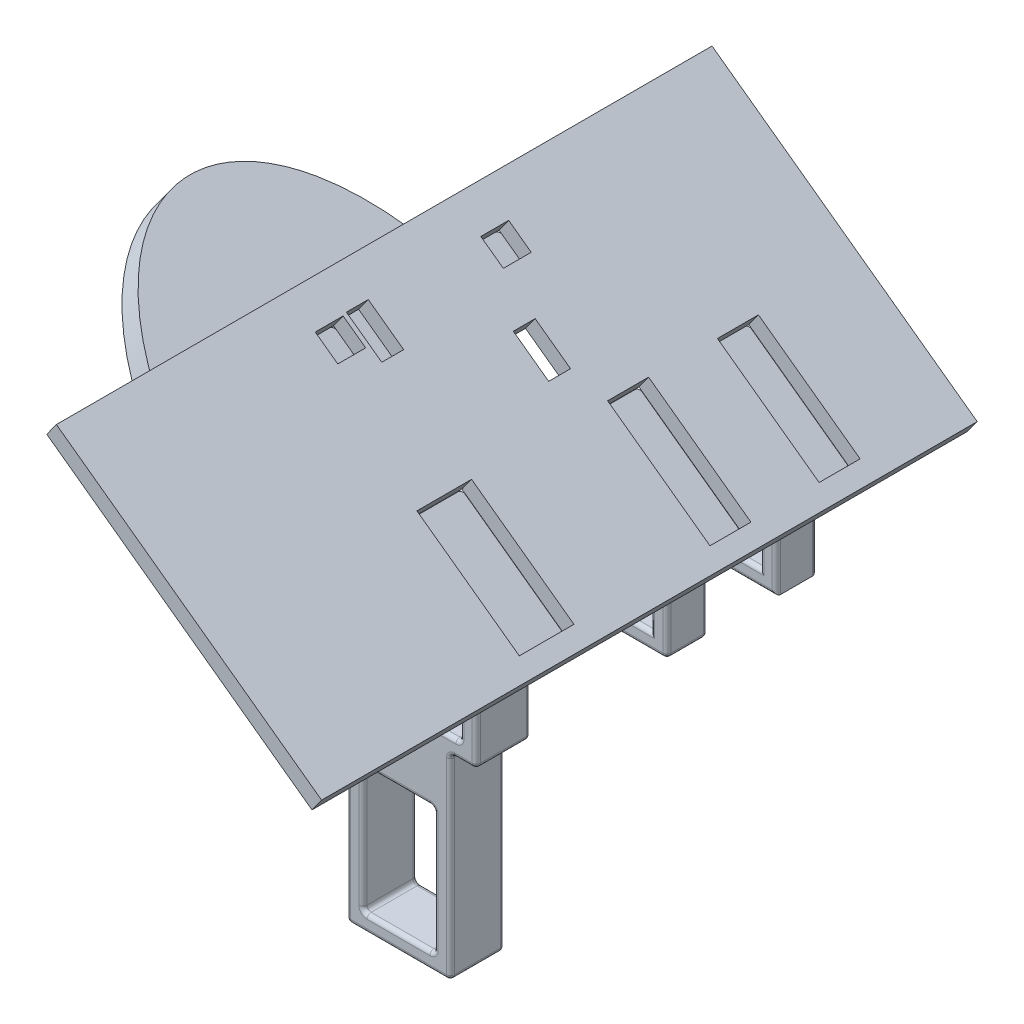
SolidWorks part; units mm, degrees
ref_plane "Front Plane" through (0, 0, 0) normal (0, 0, 1) x (1, 0, 0)
ref_plane "Top Plane" through (0, 0, 0) normal (0, 1, 0) x (1, 0, 0)
ref_plane "Right Plane" through (0, 0, 0) normal (1, 0, 0) x (0, 0, -1)
sketch "Sketch3" plane through (0, 0, 0) normal (0, 0, 1) x (1, 0, 0)
  line L0 (-14.25, 5.65) -> (14.25, 5.65) construction
  line L1 (-11.25, -2.65) -> (11.25, -2.65)
  line L2 (-11.25, -2.65) -> (-11.25, 2.65)
  line L3 (-11.25, 2.65) -> (11.25, 2.65)
  line L4 (11.25, -2.65) -> (11.25, 2.65)
  line L5 (-11.25, -2.65) -> (11.25, 2.65) construction
  line L6 (-11.25, 2.65) -> (11.25, -2.65) construction
  line L7 (-6.5, -15.45) -> (6.5, -15.45)
  line L8 (-6.5, -15.45) -> (-6.5, -38.55)
  line L9 (-6.5, -38.55) -> (6.5, -38.55)
  line L10 (6.5, -15.45) -> (6.5, -38.55)
  line L11 (-6.5, -15.45) -> (6.5, -38.55) construction
  line L12 (-6.5, -38.55) -> (6.5, -15.45) construction
  line L13 (14.25, -5.65) -> (14.25, 5.65)
  line L15 (-14.25, -5.65) -> (-14.25, 5.65)
  line L16 (9.5, -12.45) -> (9.5, -41.55)
  line L17 (-9.5, -41.55) -> (9.5, -41.55)
  line L18 (-9.5, -12.45) -> (-9.5, -41.55)
  line L20 (-9.5, -12.45) -> (9.5, -12.45) construction
  line L21 (-14.25, -5.65) -> (14.25, -5.65) construction
  line L22 (-9.5, -12.45) -> (-9.5, -5.65)
  line L23 (-9.5, -5.65) -> (-14.25, -5.65)
  line L24 (14.25, -5.65) -> (9.5, -5.65)
  line L25 (9.5, -5.65) -> (9.5, -12.45)
  line L26 (-14.25, 5.65) -> (1.7036, 27.6082)
  line L27 (1.7036, 27.6082) -> (20.3571, 14.0557)
  line L28 (20.3571, 14.0557) -> (14.25, 5.65)
  line L29 (0, -41.55) -> (0, 5.7) construction
  point P0 (0, 0)
  point P5 (0, -27)
  dimension "D1" = 22.5
  dimension "D2" = 5.3
  dimension "D3" = 27
  dimension "D4" = 13
  dimension "D5" = 23.1
  dimension "D7" = 3
  dimension "D8" = 54
  dimension "D9" = 10.39
  dimension "D10" = 8.4057
  dimension "D11" = 19
  dimension "D6" = 3
extrude "Boss-Extrude1" add sketch "Sketch3" along normal blind 9.9
sketch "Sketch4" plane through (13.7171, 18.8799, 0) normal (0.5878, 0.809, 0) x (0.809, -0.5878, 0)
  line L0 (-3.321, 0) -> (-3.321, -9.9) construction
  line L1 (8.2075, 0) -> (-14.8495, 0) construction
  line L2 (8.2075, -9.9) -> (-14.8495, -9.9) construction
  line L3 (-14.8495, -4.95) -> (8.2075, -4.95) construction
  line L4 (-14.8495, -9.9) -> (-14.8495, 0) construction
  line L5 (8.2075, -9.9) -> (8.2075, 0) construction
  line L7 (-48.321, 71.1) -> (11.679, 71.1)
  line L8 (-48.321, 71.1) -> (-48.321, -48.9)
  line L9 (-48.321, -48.9) -> (11.679, -48.9)
  line L10 (11.679, 71.1) -> (11.679, -48.9)
  line L11 (-48.321, 71.1) -> (11.679, -48.9) construction
  line L12 (-48.321, -48.9) -> (11.679, 71.1) construction
  point P12 (-3.321, -4.95)
  point P13 (-18.321, 11.1)
  dimension "D1" = 120
  dimension "D2" = 60
  dimension "D3" = 16.05
  dimension "D4" = 15
extrude "Boss-Extrude2" add sketch "Sketch4" along normal blind 3
sketch "Sketch7" plane through (13.7171, 18.8799, 0) normal (-0.5878, -0.809, 0) x (0.809, -0.5878, 0)
  line L0 (-14.9179, -11.1) -> (-63.9179, -11.1) construction
  line L1 (-48.321, 48.9) -> (11.679, 48.9) construction
  line L6 (-36.7569, 1.65) -> (-41.8569, 1.65)
  line L7 (-36.7569, 1.65) -> (-36.7569, 6.75)
  line L8 (-36.7569, 6.75) -> (-41.8569, 6.75)
  line L9 (-41.8569, 1.65) -> (-41.8569, 6.75)
  line L10 (-36.7569, 1.65) -> (-41.8569, 6.75) construction
  line L11 (-36.7569, 6.75) -> (-41.8569, 1.65) construction
  line L12 (-48.321, -71.1) -> (-48.321, 48.9) construction
  line L13 (-36.7569, -23.55) -> (-36.7569, -28.65)
  line L14 (-36.7569, -23.55) -> (-41.8569, -23.55)
  line L15 (-41.8569, -23.55) -> (-41.8569, -28.65)
  line L16 (-36.7569, -28.65) -> (-41.8569, -28.65)
  line L17 (-41.8569, -23.55) -> (-36.7569, -28.65) construction
  point P4 (-39.3069, 3.9)
  point P10 (-39.3069, -26.1)
  point P11 (-39.3069, 4.2)
  dimension "D1" = 15
  dimension "D2" = 9.0141
  dimension "D3" = 5.1
  dimension "D4" = 5.1
  dimension "D5" = 5.1
  dimension "D6" = 6.4641
  dimension "D7" = 12.45
  dimension "D8" = 60
  dimension "D9" = 30.3
extrude "Boss-Extrude3" add sketch "Sketch7" along normal blind 24.5 and the other way blind 3
sketch "Sketch8" plane through (-0.6837, -0.941, 0) normal (-0.5878, -0.809, 0) x (0.809, -0.5878, 0)
  line L2 (-23.3069, 5.8504) -> (-23.3069, -28.0504)
  line L3 (-23.3069, 5.8504) -> (-34.6206, 17.1641)
  line L4 (-23.3069, -28.0504) -> (-34.6206, -39.3641)
  line L6 (11.679, -71.1) -> (-48.321, -71.1) construction
  line L7 (-48.321, 48.9) -> (11.679, -71.1) construction
  line L8 (-18.321, -11.1) -> (-48.321, -11.1) construction
  line L9 (11.679, 48.9) -> (11.679, -71.1) construction
  ellipse E0 centre (-23.3069, -11.1) end of major axis (-72.2778, -11.1) minor radius 29.05 (-34.6206, 17.1641) -> (-34.6206, -39.3641) ccw
  dimension "D1" = 4.9859
  dimension "D2" = 28.2641
  dimension "D3" = 23.9569
  dimension "D4" = 45
  dimension "D5" = 16
  dimension "D6" = 48.9709
  dimension "D7" = 60
  dimension "D8" = 34.9859
extrude "Boss-Extrude4" add sketch "Sketch8" along normal blind 5
ref_plane "Plane1" through (0, 0, -25) normal (0, 0, -1) x (-1, 0, 0)
ref_plane "Plane2" through (0, 0, -45) normal (0, 0, -1) x (-1, 0, 0)
sketch "Sketch9" plane through (0, 0, -25) normal (0, 0, -1) x (-1, 0, 0)
  line L0 (-22.1204, 16.4827) -> (-14.25, 5.65)
  line L2 (-3.467, 30.0353) -> (14.25, 5.65)
  line L3 (14.25, 5.65) -> (14.25, -5.65)
  line L4 (14.25, -5.65) -> (9.5, -5.65)
  line L5 (9.5, -5.65) -> (-14.25, -5.65)
  line L6 (-14.25, -5.65) -> (-14.25, 5.65)
  line L7 (-11.25, 2.65) -> (11.25, 2.65)
  line L8 (11.25, 2.65) -> (11.25, -2.65)
  line L9 (11.25, -2.65) -> (-11.25, -2.65)
  line L10 (-11.25, -2.65) -> (-11.25, 2.65)
  line L12 (-24.929, 14.4422) -> (-23.1656, 12.0152) construction
  line L13 (-24.929, 14.4422) -> (23.6121, 49.7094) construction
  line L14 (-22.1204, 16.4827) -> (-3.467, 30.0353)
  dimension "D1" = 3.4715
extrude "Boss-Extrude5" add sketch "Sketch9" along normal blind 7.4 contours L10 L9 L8 L7 | L0 L6 L5 L4 L3 L2 L14 region at (0, 0, -25)
sketch "Sketch10" plane through (0, 0, -45) normal (0, 0, -1) x (-1, 0, 0)
  line L0 (-22.1204, 16.4827) -> (-14.25, 5.65)
  line L1 (-22.1204, 16.4827) -> (-3.467, 30.0353)
  line L2 (-3.467, 30.0353) -> (14.25, 5.65)
  line L3 (14.25, 5.65) -> (14.25, -5.65)
  line L6 (-14.25, -5.65) -> (-14.25, 5.65)
  line L7 (-11.25, 2.65) -> (11.25, 2.65)
  line L8 (11.25, 2.65) -> (11.25, -2.65)
  line L9 (11.25, -2.65) -> (-11.25, -2.65)
  line L10 (-11.25, -2.65) -> (-11.25, 2.65)
  line L11 (-24.929, 14.4422) -> (23.6121, 49.7094) construction
  line L13 (-20.3571, 14.0557) -> (-14.25, 5.65) construction
  line L14 (-14.25, -5.65) -> (-14.25, 5.65) construction
  line L16 (-1.7036, 27.6082) -> (14.25, 5.65) construction
  line L17 (14.25, 5.65) -> (14.25, -5.65) construction
  line L18 (-14.25, -5.65) -> (14.25, -5.65)
extrude "Boss-Extrude6" add sketch "Sketch10" along normal blind 7.4
sketch "Sketch11" plane through (13.7171, 18.8799, 0) normal (-0.5878, -0.809, 0) x (0.809, -0.5878, 0)
  line L0 (-14.8495, 9.9) -> (-14.8495, 0) construction
  line L9 (8.2075, 9.9) -> (8.2075, 0) construction
  line L10 (-48.321, 48.9) -> (11.679, 48.9) construction
  line L11 (-14.8495, -32.4) -> (-14.8495, -25) construction
  line L12 (11.679, 48.9) -> (11.679, -71.1) construction
  line L13 (8.2075, 9.9) -> (-14.8495, 9.9) construction
  line L24 (-14.901, 9.95) -> (8.259, 9.95)
  line L25 (-14.901, 9.95) -> (-14.901, -0.05)
  line L26 (-14.901, -0.05) -> (8.259, -0.05)
  line L27 (8.259, 9.95) -> (8.259, -0.05)
  line L28 (-37.611, 48.9) -> (-37.611, -71.1) construction
  line L29 (8.2075, 0) -> (-14.8495, 0) construction
  line L30 (-14.8995, -24.95) -> (8.2575, -24.95)
  line L35 (-14.8995, -24.95) -> (-14.8995, -32.45)
  line L36 (-14.8995, -32.45) -> (8.2575, -32.45)
  line L37 (8.2575, -24.95) -> (8.2575, -32.45)
  line L38 (-14.8495, -32.4) -> (8.2075, -32.4) construction
  line L39 (8.2075, -32.4) -> (8.2075, -25) construction
  line L40 (-14.8495, -25) -> (8.2075, -25) construction
  line L42 (-14.771, -44.95) -> (8.229, -44.95)
  line L43 (-14.771, -44.95) -> (-14.771, -52.45)
  line L44 (-14.771, -52.45) -> (8.229, -52.45)
  line L45 (8.229, -44.95) -> (8.229, -52.45)
  line L46 (11.679, -71.1) -> (-48.321, -71.1) construction
  line L47 (-14.8495, -45) -> (-14.8495, -52.4) construction
  line L48 (-14.8495, -52.4) -> (8.2075, -52.4) construction
  point P20 (-37.611, -11.1)
  dimension "D2" = 38.95
  dimension "D3" = 3.42
  dimension "D4" = 23.16
  dimension "D5" = 23.157
  dimension "D6" = 7.5
  dimension "D7" = 3.45
  dimension "D8" = 23
  dimension "D9" = 3.4215
  dimension "D10" = 7.5
  dimension "D11" = 73.85
  dimension "D12" = 18.65
  dimension "D13" = 10
  dimension "D14" = 0.0515
  dimension "D15" = 0.0515
  dimension "D16" = 0.05
  dimension "D17" = 0.05
  dimension "D18" = 0.05
  dimension "D19" = 0.05
  dimension "D20" = 0.05
  dimension "D21" = 0.05
  dimension "D22" = 0.0785
  dimension "D23" = 0.05
  dimension "D24" = 13.85
  dimension "D25" = 33.85
extrude "Cut-Extrude4" cut sketch "Sketch7<2>" against normal blind 10
sketch "Sketch7<2>" plane through (13.7171, 18.8799, 0) normal (-0.5878, -0.809, 0) x (0.809, -0.5878, 0) same geometry as "Sketch7"
sketch "Sketch6" plane through (13.7171, 18.8799, 0) normal (-0.5878, -0.809, 0) x (0.809, -0.5878, 0)
  line L1 (-20.971, -23.075) -> (-28.971, -23.075)
  line L2 (-20.971, -23.075) -> (-20.971, -19.075)
  line L3 (-20.971, -19.075) -> (-28.971, -19.075)
  line L4 (-28.971, -23.075) -> (-28.971, -19.075)
  line L5 (-34.071, -3.125) -> (-42.071, -3.125)
  line L6 (-34.071, -3.125) -> (-34.071, 0.875)
  line L7 (-34.071, 0.875) -> (-42.071, 0.875)
  line L10 (-48.321, -71.1) -> (-48.321, 48.9) construction
  line L11 (-42.071, 0.875) -> (-42.071, -3.125)
  line L12 (-48.321, 48.9) -> (11.679, 48.9) construction
  dimension "D1" = 8
  dimension "D2" = 6.25
  dimension "D3" = 4
  dimension "D4" = 48.025
  dimension "D5" = 15.95
  dimension "D6" = 19.35
  dimension "D7" = 8
  dimension "D8" = 4
extrude "Cut-Extrude1" cut sketch "Sketch6" against normal up to surface (3 mm away) up to face at (-16.3195, 44.411, 4.2)
fillet "Fillet1" radius 0.75 50 edges at (-11.25, 0, 9.9) (-11.25, 0, 0) (-11.875, -5.65, 9.9) (-11.875, -5.65, 0) (11.875, -5.65, 9.9) (11.875, -5.65, 0) (0, -38.55, 9.9) (0, -38.55, 0) (-6.5, -38.55, 4.95) (-6.5, -27, 9.9) (-6.5, -27, 0) (6.5, -27, 9.9) (6.5, -38.55, 4.95) (6.5, -27, 0) (-6.5, -15.45, 4.95) (0, -15.45, 9.9) (6.5, -15.45, 4.95) (0, -15.45, 0) (0, -41.55, 9.9) (0, -41.55, 0) (9.5, -41.55, 4.95) (9.5, -23.6, 9.9) (9.5, -5.65, 4.95) (9.5, -23.6, 0) (14.25, -5.65, 4.95) (14.25, 0, 9.9) (14.25, 5.65, 4.95) (14.25, 0, 0) (-9.5, -5.65, 4.95) (-9.5, -23.6, 9.9) (-9.5, -41.55, 4.95) (-9.5, -23.6, 0) (-14.25, 5.65, 4.95) (-14.25, 0, 9.9) (-14.25, -5.65, 4.95) (-14.25, 0, 0) (11.25, 0, 9.9) (11.25, 0, 0) (-11.25, 2.65, 4.95) (0, 2.65, 9.9) (11.25, 2.65, 4.95) (0, 2.65, 0) (11.25, -2.65, 4.95) (0, -2.65, 9.9) (-11.25, -2.65, 4.95) (0, -2.65, 0) (17.3035, 9.8528, 9.9) (17.3035, 9.8528, 0) (-6.2732, 16.6291, 9.9) (-6.2732, 16.6291, 0)
fillet "Fillet4" radius 0.75 48 edges at (14.25, 5.65, -48.7) (-14.25, 5.65, -48.7) (17.3035, 9.8528, -45) (14.25, 0, -45) (-14.25, 0, -45) (-6.2732, 16.6291, -45) (-11.25, 0, -45) (0, -2.65, -45) (11.25, 0, -45) (0, 2.65, -45) (-14.25, 0, -52.4) (14.25, 0, -52.4) (17.3035, 9.8528, -52.4) (-6.2732, 16.6291, -52.4) (0, -2.65, -52.4) (-11.25, 0, -52.4) (0, 2.65, -52.4) (11.25, 0, -52.4) (-11.25, -2.65, -48.7) (11.25, 2.65, -48.7) (-11.25, 2.65, -48.7) (-14.25, -5.65, -48.7) (0, -5.65, -45) (0, -5.65, -52.4) (17.3035, 9.8528, -25) (-14.25, -5.65, -28.7) (-14.25, 0, -32.4) (-14.25, 5.65, -28.7) (-14.25, 0, -25) (-6.2732, 16.6291, -25) (11.25, 2.65, -28.7) (11.25, 0, -25) (0, 2.65, -25) (-11.25, -2.65, -28.7) (0, -5.65, -25) (-11.25, 0, -25) (0, -2.65, -25) (-11.25, 0, -32.4) (14.25, -5.65, -28.7) (14.25, 5.65, -28.7) (14.25, 0, -25) (14.25, 0, -32.4) (17.3035, 9.8528, -32.4) (-6.2732, 16.6291, -32.4) (0, -5.65, -32.4) (0, -2.65, -32.4) (11.25, 0, -32.4) (0, 2.65, -32.4)
chamfer "Chamfer1" distance 2 angle 45 8 edges at (-32.4836, 22.163, 1.65) (-30.4206, 20.6642, 4.2) (-32.4836, 22.163, 6.75) (-34.5466, 23.6619, 4.2) (-32.4836, 22.163, -23.55) (-30.4206, 20.6642, -26.1) (-32.4836, 22.163, -28.65) (-34.5466, 23.6619, -26.1)
fillet "Fillet6" radius 0.75 8 edges at (-22.6325, 31.3837, 1.65) (-22.6325, 31.3837, 6.75) (-26.7584, 34.3814, 1.65) (-26.7584, 34.3814, 6.75) (-22.6325, 31.3837, -23.55) (-26.7584, 34.3814, -23.55) (-22.6325, 31.3837, -28.65) (-26.7584, 34.3814, -28.65)
extrude "Cut-Extrude5" cut sketch "Sketch11" against normal blind 10
